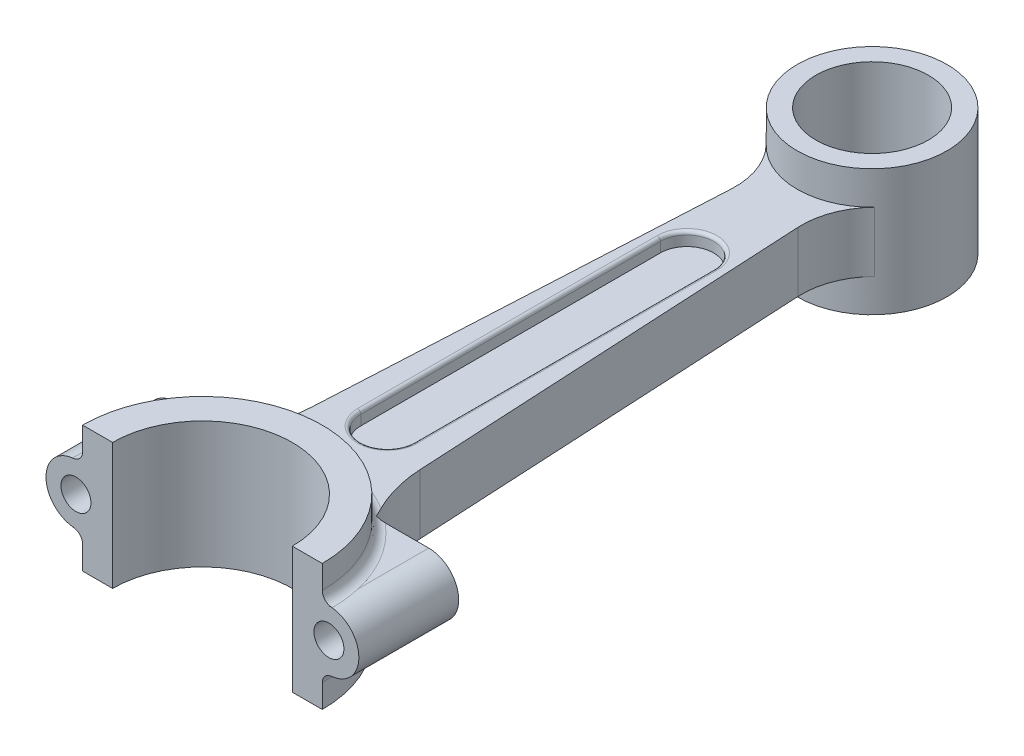
SolidWorks part; units mm, degrees
ref_plane "Front Plane" through (0, 0, 0) normal (0, 0, 1) x (1, 0, 0)
ref_plane "Top Plane" through (0, 0, 0) normal (0, 1, 0) x (1, 0, 0)
ref_plane "Right Plane" through (0, 0, 0) normal (1, 0, 0) x (0, 0, -1)
sketch "Sketch1" plane through (0, 0, 0) normal (0, 1, 0) x (1, 0, 0)
  line L0 (0, 0) -> (0, 201.2) construction
  line L1 (79.7176, 0) -> (-79.7176, 0) construction
  line L2 (-36, 0) -> (-27, 0)
  line L3 (27, 0) -> (36, 0)
  line L4 (-16.2797, 49.0413) -> (-10, 168.8655)
  line L5 (16.2797, 49.0413) -> (10, 168.8655)
  line L6 (0, 55.6) -> (0, 145.6) construction
  line L7 (-8, 55.6) -> (-8, 145.6)
  line L8 (8, 55.6) -> (8, 145.6)
  arc A0 (27, 0) -> (-27, 0) centre (0, 0) ccw
  arc A1 (36, 0) -> (-36, 0) centre (0, 0) ccw
  circle A2 centre (0, 201.2) radius 22.5
  circle A3 centre (0, 201.2) radius 16.9
  arc A4 (-16.2797, 49.0413) -> (-26.6328, 24.2217) centre (-56.2249, 51.1347) cw
  arc A5 (-10, 168.8655) -> (-16.2346, 185.6215) centre (-32.4692, 170.0431) ccw
  arc A6 (16.2797, 49.0413) -> (26.6328, 24.2217) centre (56.2249, 51.1347) ccw
  arc A7 (10, 168.8655) -> (16.2346, 185.6215) centre (32.4692, 170.0431) cw
  arc A8 (-8, 55.6) -> (8, 55.6) centre (0, 55.6) ccw
  arc A9 (8, 145.6) -> (-8, 145.6) centre (0, 145.6) ccw
  point P8 (0, 0)
  point P26 (0, 100.6)
  point P32 (0, 100.6)
  dimension "D1" = 27
  dimension "D2" = 36
  dimension "D3" = 45
  dimension "D4" = 33.8
  dimension "D7" = 40
  dimension "D10" = 22.5
  dimension "D11" = 8
  dimension "D5" = 201.2
  dimension "D6" = 6
  dimension "D8" = 90
  dimension "D9" = 20
extrude "Boss-Extrude1" add sketch "Sketch1" along normal mid plane 38 contours A2 A3 | L3 A1 L2 A0 region at (-32.8259, 0, -12.6946) region at (-8.1581, 0, -221.4845)
extrude "Boss-Extrude2" add sketch "Sketch1<3>" along normal mid plane 18 contours L5 A7 A2 A5 L4 A4 A1 A6 A9 L8 A8 L7 region at (-17.7394, 0, -35.081)
sketch "Sketch1<3>" plane through (0, 0, 0) normal (0, 1, 0) x (1, 0, 0) same geometry as "Sketch1"
extrude "Boss-Extrude3" add sketch "Sketch1<4>" along normal mid plane 10 contours L8 A9 L7 A8 region at (0, 0, -100.6)
sketch "Sketch1<4>" plane through (0, 0, 0) normal (0, 1, 0) x (1, 0, 0) same geometry as "Sketch1"
fillet "Fillet2" radius 1 8 edges at (8, 9, -100.6) (0, 9, -47.6) (-8, 9, -100.6) (8, -9, -100.6) (0, -9, -47.6) (-8, -9, -100.6) (0, 9, -153.6) (0, -9, -153.6)
sketch "Sketch3" plane through (0, 0, 0) normal (0, 1, 0) x (1, 0, 0)
  line L0 (-19.8997, 30) -> (-49, 30)
  line L1 (-49, 30) -> (-49, 0)
  line L2 (-49, 0) -> (-36, 0)
  line L3 (79.7176, 0) -> (-79.7176, 0) construction
  line L4 (0, -20.9) -> (0, 20.9) construction
  line L5 (49, 30) -> (49, 0)
  line L6 (19.8997, 30) -> (49, 30)
  line L7 (49, 0) -> (36, 0)
  arc A0 (-36, 0) -> (-19.8997, 30) centre (0, 0) cw
  arc A1 (36, 0) -> (-36, 0) centre (0, 0) ccw construction
  arc A2 (36, 0) -> (19.8997, 30) centre (0, 0) ccw
  point P20 (-42.5, 0)
  point P21 (42.5, 0)
  dimension "D1" = 30
  dimension "D2" = 85
extrude "Boss-Extrude4" add sketch "Sketch3" along normal mid plane 18
fillet "Fillet3" radius 3 2 edges at (0, -9, -36) (0, 9, -36)
sketch "Sketch5" plane through (0, 0, 0) normal (0, 0, 1) x (1, 0, 0)
  line L0 (-38, -12.9004) -> (-38, 12.9004) construction
  line L1 (0, -20.9) -> (0, 20.9) construction
  line L2 (38, -12.9004) -> (38, 12.9004) construction
  line L3 (-38, 9) -> (-49, 9)
  line L4 (-49, 9) -> (-49, -9)
  line L5 (-49, -9) -> (-38, -9)
  line L6 (-49, 9) -> (-39, 9) construction
  line L7 (49, -9) -> (38, -9)
  line L8 (49, 9) -> (49, -9)
  line L9 (38, 9) -> (49, 9)
  circle A0 centre (-38, 0) radius 4.5
  arc A1 (-38, 9) -> (-38, -9) centre (-38, 0) ccw
  arc A2 (38, 9) -> (38, -9) centre (38, 0) cw
  circle A3 centre (38, 0) radius 4.5
  line M13 (39, -9) -> (49, -9)
  line M14 (49, -9) -> (49, 9)
  line M15 (49, 9) -> (39, 9)
  dimension "D1" = 9
  dimension "D2" = 9
  dimension "D3" = 76
extrude "Cut-Extrude1" cut sketch "Sketch5" against normal blind 38 contours L9 A2 L7 M13 M14 M15 | A1 L3 L4 L5 | A3 | A0 | L7 A2 L9 L8 region at (-47.211, 0, 0) region at (44, -8.789, 0) region at (-38, 0, 0) region at (38, 0, 0)
